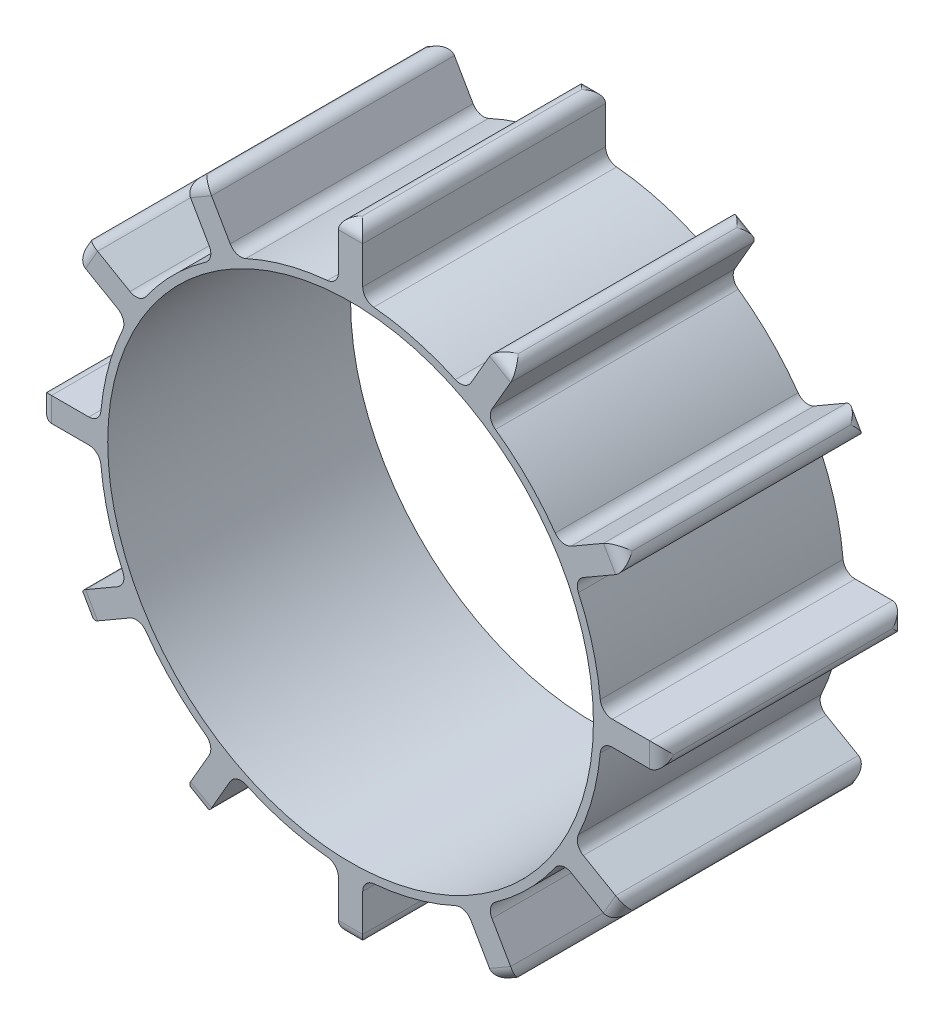
SolidWorks part; units mm, degrees
ref_plane "Ebene vorne" through (0, 0, 0) normal (0, 0, 1) x (1, 0, 0)
ref_plane "Ebene oben" through (0, 0, 0) normal (0, 1, 0) x (1, 0, 0)
ref_plane "Ebene rechts" through (0, 0, 0) normal (1, 0, 0) x (0, 0, -1)
sketch "Skizze1" plane through (0, 0, 0) normal (0, 0, 1) x (1, 0, 0)
  line L0 (0, 0) -> (-20.65, 0) construction
  line L1 (-20.65, 0) -> (-23.1258, 0) construction
  line L2 (-22.6926, 11.9469) -> (-18.3624, 9.4469)
  line L3 (-25.6258, 1) -> (-20.6258, 1)
  line L4 (-25.6258, 1) -> (-25.6258, -1)
  line L5 (-25.6258, -1) -> (-20.6258, -1)
  line L7 (-25.6258, 1) -> (-20.6258, -1) construction
  line L8 (-25.6258, -1) -> (-20.6258, 1) construction
  line L9 (-21.6926, 13.6789) -> (-22.6926, 11.9469)
  line L10 (-21.6926, 13.6789) -> (-17.3624, 11.1789)
  line L11 (-21.6926, 13.6789) -> (-18.3624, 9.4469) construction
  line L12 (-22.6926, 11.9469) -> (-17.3624, 11.1789) construction
  line L13 (-13.6789, 21.6926) -> (-11.1789, 17.3624)
  line L14 (-11.9469, 22.6926) -> (-13.6789, 21.6926)
  line L15 (-11.9469, 22.6926) -> (-9.4469, 18.3624)
  line L16 (-11.9469, 22.6926) -> (-11.1789, 17.3624) construction
  line L17 (-13.6789, 21.6926) -> (-9.4469, 18.3624) construction
  line L18 (-1, 25.6258) -> (-1, 20.6258)
  line L19 (1, 25.6258) -> (-1, 25.6258)
  line L20 (1, 25.6258) -> (1, 20.6258)
  line L21 (1, 25.6258) -> (-1, 20.6258) construction
  line L22 (-1, 25.6258) -> (1, 20.6258) construction
  line L23 (11.9469, 22.6926) -> (9.4469, 18.3624)
  line L24 (13.6789, 21.6926) -> (11.9469, 22.6926)
  line L25 (13.6789, 21.6926) -> (11.1789, 17.3624)
  line L26 (13.6789, 21.6926) -> (9.4469, 18.3624) construction
  line L27 (11.9469, 22.6926) -> (11.1789, 17.3624) construction
  line L28 (21.6926, 13.6789) -> (17.3624, 11.1789)
  line L29 (22.6926, 11.9469) -> (21.6926, 13.6789)
  line L30 (22.6926, 11.9469) -> (18.3624, 9.4469)
  line L31 (22.6926, 11.9469) -> (17.3624, 11.1789) construction
  line L32 (21.6926, 13.6789) -> (18.3624, 9.4469) construction
  line L33 (25.6258, 1) -> (20.6258, 1)
  line L34 (25.6258, -1) -> (25.6258, 1)
  line L35 (25.6258, -1) -> (20.6258, -1)
  line L36 (25.6258, -1) -> (20.6258, 1) construction
  line L37 (25.6258, 1) -> (20.6258, -1) construction
  line L38 (22.6926, -11.9469) -> (18.3624, -9.4469)
  line L39 (21.6926, -13.6789) -> (22.6926, -11.9469)
  line L40 (21.6926, -13.6789) -> (17.3624, -11.1789)
  line L41 (21.6926, -13.6789) -> (18.3624, -9.4469) construction
  line L42 (22.6926, -11.9469) -> (17.3624, -11.1789) construction
  line L43 (13.6789, -21.6926) -> (11.1789, -17.3624)
  line L44 (11.9469, -22.6926) -> (13.6789, -21.6926)
  line L45 (11.9469, -22.6926) -> (9.4469, -18.3624)
  line L46 (11.9469, -22.6926) -> (11.1789, -17.3624) construction
  line L47 (13.6789, -21.6926) -> (9.4469, -18.3624) construction
  line L48 (1, -25.6258) -> (1, -20.6258)
  line L49 (-1, -25.6258) -> (1, -25.6258)
  line L50 (-1, -25.6258) -> (-1, -20.6258)
  line L51 (-1, -25.6258) -> (1, -20.6258) construction
  line L52 (1, -25.6258) -> (-1, -20.6258) construction
  line L53 (-11.9469, -22.6926) -> (-9.4469, -18.3624)
  line L54 (-13.6789, -21.6926) -> (-11.9469, -22.6926)
  line L55 (-13.6789, -21.6926) -> (-11.1789, -17.3624)
  line L56 (-13.6789, -21.6926) -> (-9.4469, -18.3624) construction
  line L57 (-11.9469, -22.6926) -> (-11.1789, -17.3624) construction
  line L58 (-21.6926, -13.6789) -> (-17.3624, -11.1789)
  line L59 (-22.6926, -11.9469) -> (-21.6926, -13.6789)
  line L60 (-22.6926, -11.9469) -> (-18.3624, -9.4469)
  line L61 (-22.6926, -11.9469) -> (-17.3624, -11.1789) construction
  line L62 (-21.6926, -13.6789) -> (-18.3624, -9.4469) construction
  circle A0 centre (0, 0) radius 20
  arc A1 (-20.6258, -1) -> (-18.3624, -9.4469) centre (0, 0) ccw
  arc A2 (-9.4469, -18.3624) -> (-1, -20.6258) centre (0, 0) ccw
  arc A3 (-17.3624, -11.1789) -> (-11.1789, -17.3624) centre (0, 0) ccw
  arc A4 (1, -20.6258) -> (9.4469, -18.3624) centre (0, 0) ccw
  arc A5 (11.1789, -17.3624) -> (17.3624, -11.1789) centre (0, 0) ccw
  arc A6 (18.3624, -9.4469) -> (20.6258, -1) centre (0, 0) ccw
  arc A7 (20.6258, 1) -> (18.3624, 9.4469) centre (0, 0) ccw
  arc A8 (17.3624, 11.1789) -> (11.1789, 17.3624) centre (0, 0) ccw
  arc A9 (9.4469, 18.3624) -> (1, 20.6258) centre (0, 0) ccw
  arc A10 (-1, 20.6258) -> (-9.4469, 18.3624) centre (0, 0) ccw
  arc A11 (-11.1789, 17.3624) -> (-17.3624, 11.1789) centre (0, 0) ccw
  arc A12 (-18.3624, 9.4469) -> (-20.6258, 1) centre (0, 0) ccw
  point P55 (0, 0)
  dimension "D1" = 40
  dimension "D2" = 41.3
  dimension "D3" = 5
  dimension "D4" = 2
  dimension "D5" = 2.4758
  dimension "D6" = 12
extrude "Aufsatz-Linear austragen2" add sketch "Skizze1" along normal blind 20
fillet "Verrundung1" radius 1 72 edges at (-25.6258, 1, 10) (-25.6258, 0, 20) (-25.6258, -1, 10) (-25.6258, 0, 0) (-21.6926, 13.6789, 10) (-22.1926, 12.8129, 20) (-22.6926, 11.9469, 10) (-22.1926, 12.8129, 0) (-22.6926, -11.9469, 10) (-22.1926, -12.8129, 20) (-21.6926, -13.6789, 10) (-22.1926, -12.8129, 0) (-13.6789, -21.6926, 10) (-12.8129, -22.1926, 20) (-11.9469, -22.6926, 10) (-12.8129, -22.1926, 0) (-1, -25.6258, 10) (0, -25.6258, 20) (1, -25.6258, 10) (0, -25.6258, 0) (11.9469, -22.6926, 10) (12.8129, -22.1926, 20) (13.6789, -21.6926, 10) (12.8129, -22.1926, 0) (21.6926, -13.6789, 10) (22.1926, -12.8129, 20) (22.6926, -11.9469, 10) (22.1926, -12.8129, 0) (25.6258, -1, 10) (25.6258, 0, 20) (25.6258, 1, 10) (25.6258, 0, 0) (22.6926, 11.9469, 10) (22.1926, 12.8129, 20) (21.6926, 13.6789, 10) (22.1926, 12.8129, 0) (13.6789, 21.6926, 10) (12.8129, 22.1926, 20) (11.9469, 22.6926, 10) (12.8129, 22.1926, 0) (1, 25.6258, 10) (0, 25.6258, 20) (-1, 25.6258, 10) (0, 25.6258, 0) (-11.9469, 22.6926, 10) (-12.8129, 22.1926, 20) (-13.6789, 21.6926, 10) (-12.8129, 22.1926, 0) (-9.4469, 18.3624, 10) (1, 20.6258, 10) (11.1789, 17.3624, 10) (18.3624, 9.4469, 10) (20.6258, -1, 10) (17.3624, -11.1789, 10) (9.4469, -18.3624, 10) (-1, -20.6258, 10) (-11.1789, 17.3624, 10) (-1, 20.6258, 10) (9.4469, 18.3624, 10) (17.3624, 11.1789, 10) (20.6258, 1, 10) (18.3624, -9.4469, 10) (11.1789, -17.3624, 10) (1, -20.6258, 10) (-9.4469, -18.3624, 10) (-11.1789, -17.3624, 10) (-17.3624, -11.1789, 10) (-18.3624, -9.4469, 10) (-20.6258, -1, 10) (-20.6258, 1, 10) (-18.3624, 9.4469, 10) (-17.3624, 11.1789, 10)
